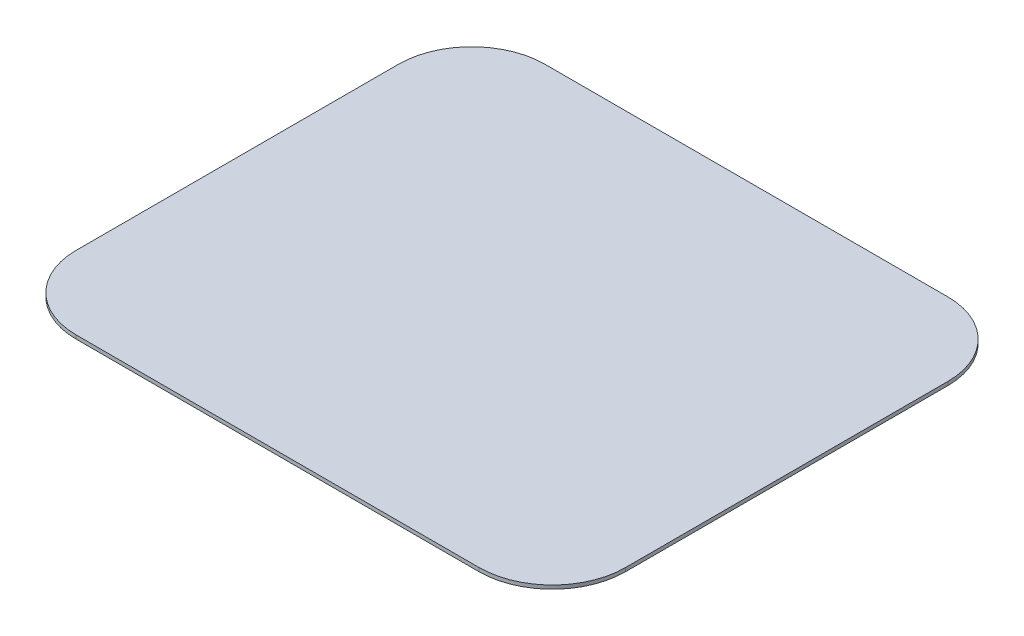
SolidWorks part; units mm, degrees
ref_plane "Front Plane" through (0, 0, 0) normal (0, 0, 1) x (1, 0, 0)
ref_plane "Top Plane" through (0, 0, 0) normal (0, 1, 0) x (1, 0, 0)
ref_plane "Right Plane" through (0, 0, 0) normal (1, 0, 0) x (0, 0, -1)
sketch "Sketch1" plane through (0, 0, 0) normal (0, 1, 0) x (1, 0, 0)
  line L1 (-92.717, 79.5943) -> (127.283, 79.5943)
  line L2 (-132.717, 39.5943) -> (-132.717, -136.4057)
  line L3 (-92.717, -176.4057) -> (127.283, -176.4057)
  line L4 (167.283, 39.5943) -> (167.283, -136.4057)
  arc A0 (127.283, 79.5943) -> (167.283, 39.5943) centre (127.283, 39.5943) cw
  arc A1 (127.283, -176.4057) -> (167.283, -136.4057) centre (127.283, -136.4057) ccw
  arc A2 (-132.717, -136.4057) -> (-92.717, -176.4057) centre (-92.717, -136.4057) ccw
  arc A3 (-132.717, 39.5943) -> (-92.717, 79.5943) centre (-92.717, 39.5943) cw
  point P6 (167.283, 79.5943)
  point P9 (167.283, -176.4057)
  point P14 (-132.717, 79.5943)
  point P21 (-60.717, -126.4057)
  point P26 (95.283, 29.5943)
  point P29 (-60.717, 29.5943)
  dimension "D3" = 40
  dimension "D1" = 300
  dimension "D2" = 256
extrude "Boss-Extrude1" add sketch "Sketch1" along normal blind 2
